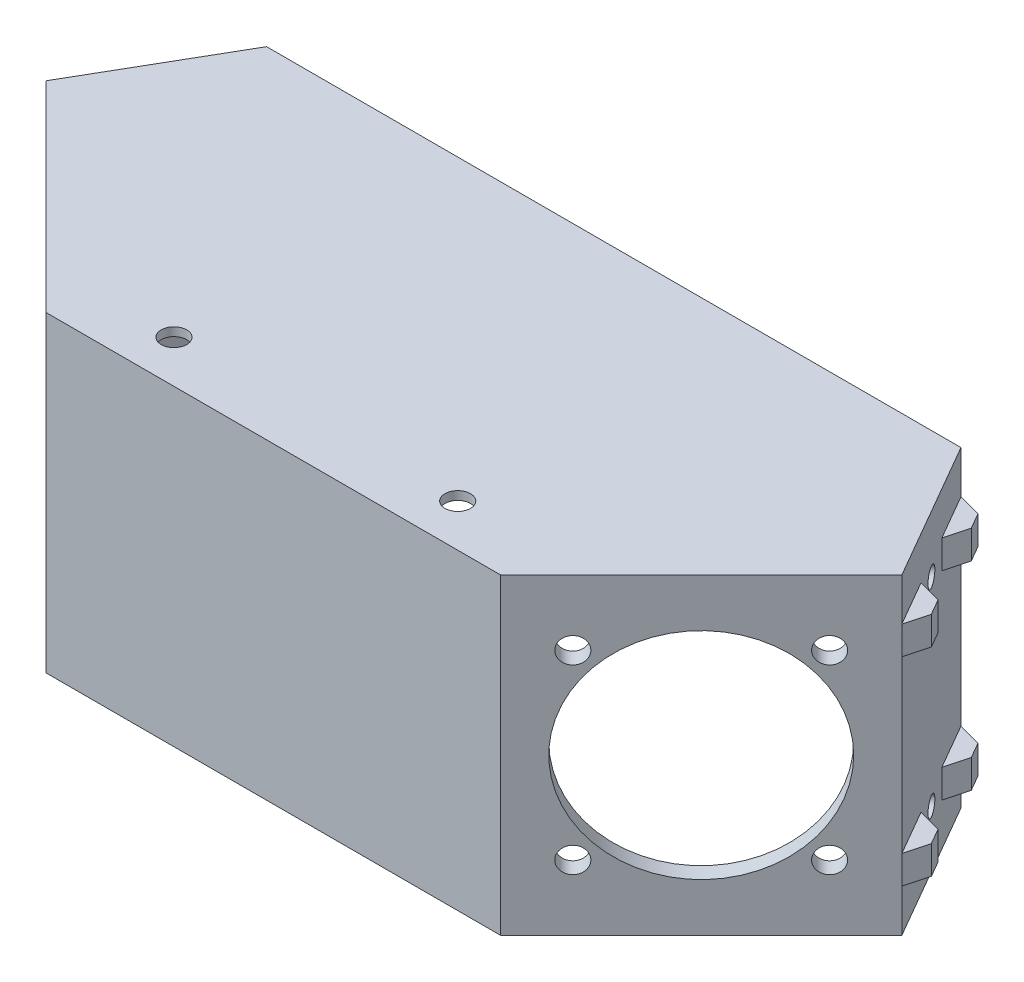
SolidWorks part; units mm, degrees
ref_plane "Front Plane" through (0, 0, 0) normal (0, 0, 1) x (1, 0, 0)
ref_plane "Top Plane" through (0, 0, 0) normal (0, 1, 0) x (1, 0, 0)
ref_plane "Right Plane" through (0, 0, 0) normal (1, 0, 0) x (0, 0, -1)
sketch "Sketch1" plane through (0, 0, 0) normal (0, 1, 0) x (1, 0, 0)
  line L0 (-30, -18) -> (30, -18) construction
  line L1 (-30, 10) -> (-22.5, 10) construction
  line L2 (-46.46, 5.4904) -> (-53.96, -7.5) construction
  line L3 (-30, -10) -> (-22.5, -10) construction
  line L4 (30, 10) -> (30, 2.5) construction
  line L5 (0, 0) -> (0, -75.5561) construction
  line L6 (38.6603, -23) -> (51.362, -45) construction
  line L7 (56.8838, -52) -> (58.3716, -51.141) construction
  line L8 (59.1036, -48.409) -> (41.8357, -18.5) construction
  line L9 (43.1036, -13.7679) -> (55.6921, -6.5) construction
  line L10 (56.4241, -3.7679) -> (51.362, 5) construction
  line L11 (25.3812, 20) -> (-25.3812, 20) construction
  line L12 (43.5677, -13.5) -> (36.0677, -0.5096) construction
  line L13 (36.0677, -0.5096) -> (46.46, 5.4904) construction
  line L14 (46.46, 5.4904) -> (53.96, -7.5) construction
  line L15 (-36.0677, -0.5096) -> (-46.46, 5.4904) construction
  line L16 (-43.5677, -13.5) -> (-36.0677, -0.5096) construction
  line L17 (-56.4241, -3.7679) -> (-51.362, 5) construction
  line L18 (-43.1036, -13.7679) -> (-55.6921, -6.5) construction
  line L19 (-59.1036, -48.409) -> (-41.8357, -18.5) construction
  line L20 (-56.8838, -52) -> (-58.3716, -51.141) construction
  line L21 (-38.6603, -23) -> (-51.362, -45) construction
  line L22 (-30, 10) -> (-30, 2.5) construction
  line L23 (30, 2.5) -> (25, 2.5) construction
  line L24 (25, 2.5) -> (25, -2.5) construction
  line L25 (25, -2.5) -> (30, -2.5) construction
  line L26 (30, -2.5) -> (30, -10) construction
  line L27 (22.5, -10) -> (22.5, -5) construction
  line L28 (22.5, -5) -> (17.5, -5) construction
  line L29 (17.5, -5) -> (17.5, -10) construction
  line L30 (22.5, -10) -> (30, -10) construction
  line L31 (17.5, 10) -> (17.5, 9) construction
  line L32 (17.5, 9) -> (22.5, 9) construction
  line L33 (22.5, 9) -> (22.5, 10) construction
  line L34 (22.5, 10) -> (30, 10) construction
  line L35 (2.5, -10) -> (2.5, -5) construction
  line L36 (2.5, -5) -> (-2.5, -5) construction
  line L37 (-2.5, -5) -> (-2.5, -10) construction
  line L38 (-2.5, 10) -> (-2.5, 9) construction
  line L39 (-2.5, 9) -> (2.5, 9) construction
  line L40 (2.5, 9) -> (2.5, 10) construction
  line L41 (-17.5, -10) -> (-17.5, -5) construction
  line L42 (-17.5, -5) -> (-22.5, -5) construction
  line L43 (-22.5, -5) -> (-22.5, -10) construction
  line L44 (-22.5, 10) -> (-22.5, 9) construction
  line L45 (-22.5, 9) -> (-17.5, 9) construction
  line L46 (-17.5, 9) -> (-17.5, 10) construction
  line L47 (-17.5, 10) -> (-2.5, 10) construction
  line L48 (-17.5, -10) -> (-2.5, -10) construction
  line L49 (2.5, -10) -> (17.5, -10) construction
  line L50 (2.5, 10) -> (17.5, 10) construction
  line L51 (-25, -2.5) -> (-30, -2.5) construction
  line L52 (-25, 2.5) -> (-25, -2.5) construction
  line L53 (-30, 2.5) -> (-25, 2.5) construction
  line L54 (-30, -2.5) -> (-30, -10) construction
  line L55 (-56.8838, -52) -> (56.8838, -52) construction
  line L56 (-49.6299, -48) -> (49.6299, -48) construction
  line L57 (40.0502, -112) -> (-40.0502, -112)
  line L58 (-75.4055, -76.6447) -> (-61.1769, -52)
  line L59 (-75.4055, -76.6447) -> (-40.0502, -112)
  line L60 (-61.1769, -52) -> (61.1769, -52)
  line L61 (61.1769, -52) -> (75.4055, -76.6447)
  line L62 (75.4055, -76.6447) -> (40.0502, -112)
  circle A0 centre (0, 0) radius 31.6228 construction
  arc A1 (30, -18) -> (38.6603, -23) centre (30, -28) cw construction
  arc A2 (51.362, 5) -> (25.3812, 20) centre (25.3812, -10) ccw construction
  arc A3 (41.1036, -13.7679) -> (40.1036, -17.5) centre (40.1036, -15.5) ccw construction
  arc A4 (58.3716, -51.141) -> (59.1036, -48.409) centre (57.3716, -49.409) ccw construction
  arc A5 (55.6921, -6.5) -> (56.4241, -3.7679) centre (54.6921, -4.7679) ccw construction
  arc A6 (40.1036, -17.5) -> (41.8357, -18.5) centre (40.1036, -19.5) cw construction
  arc A7 (41.1036, -13.7679) -> (43.1036, -13.7679) centre (42.1036, -12.0359) ccw construction
  arc A8 (-41.1036, -13.7679) -> (-43.1036, -13.7679) centre (-42.1036, -12.0359) cw construction
  arc A9 (-40.1036, -17.5) -> (-41.8357, -18.5) centre (-40.1036, -19.5) ccw construction
  arc A10 (-55.6921, -6.5) -> (-56.4241, -3.7679) centre (-54.6921, -4.7679) cw construction
  arc A11 (-58.3716, -51.141) -> (-59.1036, -48.409) centre (-57.3716, -49.409) cw construction
  arc A12 (-41.1036, -13.7679) -> (-40.1036, -17.5) centre (-40.1036, -15.5) cw construction
  arc A13 (-51.362, 5) -> (-25.3812, 20) centre (-25.3812, -10) cw construction
  arc A14 (-30, -18) -> (-38.6603, -23) centre (-30, -28) ccw construction
  arc A17 (49.6299, -48) -> (51.362, -45) centre (49.6299, -46) ccw construction
  arc A18 (-49.6299, -48) -> (-51.362, -45) centre (-49.6299, -46) cw construction
  point P7 (-57.4241, -5.5)
  point P9 (0, -18)
  point P22 (35.7735, -18)
  point P27 (0, 10)
  point P30 (60.1036, -50.141)
  point P33 (57.4241, -5.5)
  point P61 (0, 20)
  point P65 (-60.1036, -50.141)
  point P66 (-35.7735, -18)
  dimension "D12" = 10
  dimension "D14" = 30
  dimension "D16" = 2
  dimension "D17" = 2
  dimension "D28" = 60
  dimension "D29" = 2
  dimension "D32" = 45
  dimension "D2" = 30
  dimension "D3" = 5
  dimension "D4" = 8
  dimension "D5" = 40
  dimension "D6" = 20
  dimension "D7" = 30
  dimension "D8" = 10
  dimension "D9" = 4
  dimension "D10" = 12
  dimension "D11" = 15
  dimension "D13" = 20
  dimension "D15" = 34
  dimension "D18" = 5
  dimension "D19" = 2.5
  dimension "D20" = 5
  dimension "D21" = 5
  dimension "D22" = 5
  dimension "D23" = 7.5
  dimension "D24" = 1
  dimension "D26" = 20
  dimension "D27" = 4
  dimension "D30" = 50
  dimension "D31" = 45
  dimension "D33" = 50
  dimension "D25" = 3
extrude "Boss-Extrude1" add sketch "Sketch1" along normal blind 55
shell "Shell1" thickness 3 removed face at (0, 0, 80.2149) removed face at (0, 27.5, 52)
sketch "Sketch2" plane through (76.0251, 0, 76.0251) normal (0.7071, 0, 0.7071) x (0.7071, 0, -0.7071)
  line L0 (-0.8762, 27.5) -> (-25.8762, 27.5) construction
  line L1 (-0.8762, 55) -> (-0.8762, 0) construction
  line L2 (-25.8762, 27.5) -> (-25.8762, 0) construction
  line L3 (-50.8762, 0) -> (-0.8762, 0) construction
  circle A0 centre (-25.8762, 27.5) radius 19
  circle A1 centre (-41.8762, 11.5) radius 2.25
  circle A2 centre (-9.8762, 11.5) radius 2.25
  circle A3 centre (-9.8762, 43.5) radius 2.25
  circle A4 centre (-41.8762, 43.5) radius 2.25
  dimension "D1" = 38
  dimension "D2" = 4.5
  dimension "D4" = 16
  dimension "D7" = 32
  dimension "D8" = 32
  dimension "D3" = 16
  dimension "D6" = 2
  dimension "D5" = 2
extrude "Cut-Extrude1" cut sketch "Sketch2" against normal up to next
sketch "Sketch3" plane through (23.366, 0, -13.4904) normal (0.866, 0, -0.5) x (-0.5, 0, -0.866)
  line L0 (-89.8504, 55) -> (-89.8504, 0) construction
  line L1 (-104.079, 55) -> (-75.6218, 55) construction
  line L2 (-104.079, 0) -> (-75.6218, 0) construction
  circle A0 centre (-89.8504, 10) radius 1.65
  circle A1 centre (-89.8504, 45) radius 1.65
  dimension "D1" = 3.3
  dimension "D2" = 3.3
  dimension "D4" = 10
  dimension "D3" = 10
extrude "Cut-Extrude2" cut sketch "Sketch3" against normal up to next
sketch "Sketch4" plane through (23.366, 0, -13.4904) normal (0.866, 0, -0.5) x (-0.5, 0, -0.866)
  line L0 (-75.6218, 55) -> (-75.6218, 0) construction
  line L1 (-75.6218, 7.5) -> (-84.8504, 7.5)
  line L2 (-75.6218, 7.5) -> (-75.6218, 12.5)
  line L3 (-75.6218, 12.5) -> (-84.8504, 12.5)
  line L4 (-104.079, 7.5) -> (-104.079, 12.5)
  line L5 (-104.079, 55) -> (-104.079, 0) construction
  line L6 (-104.079, 0) -> (-75.6218, 0) construction
  line L7 (-75.6218, 42.5) -> (-84.8504, 42.5)
  line L8 (-75.6218, 42.5) -> (-75.6218, 47.5)
  line L9 (-75.6218, 47.5) -> (-84.8504, 47.5)
  line L10 (-104.079, 42.5) -> (-104.079, 47.5)
  line L11 (-104.079, 55) -> (-75.6218, 55) construction
  line L12 (-84.8504, 47.5) -> (-84.8504, 42.5)
  line L13 (-94.8504, 47.5) -> (-94.8504, 42.5)
  line L14 (-94.8504, 47.5) -> (-104.079, 47.5)
  line L15 (-94.8504, 42.5) -> (-104.079, 42.5)
  line L16 (-94.8504, 12.5) -> (-104.079, 12.5)
  line L17 (-94.8504, 7.5) -> (-104.079, 7.5)
  line L18 (-94.8504, 12.5) -> (-94.8504, 7.5)
  line L19 (-84.8504, 12.5) -> (-84.8504, 7.5)
  circle A0 centre (-89.8504, 45) radius 1.65 construction
  dimension "D1" = 5
  dimension "D2" = 5
  dimension "D3" = 7.5
  dimension "D4" = 7.5
  dimension "D5" = 10
  dimension "D6" = 5
extrude "Boss-Extrude2" add sketch "Sketch4" along normal blind 3
chamfer "Chamfer1" distance 3 angle 45 8 edges at (63.775, 10, 50.5) (63.775, 45, 50.5) (68.3893, 45, 58.4922) (68.3893, 10, 58.4922) (73.3893, 10, 67.1525) (73.3893, 45, 67.1525) (78.0036, 10, 75.1447) (78.0036, 45, 75.1447)
mirror "Mirror2" about plane through (0, 0, 0) normal (1, 0, 0) of "Chamfer1", "Boss-Extrude2", "Cut-Extrude2", "Cut-Extrude1"
sketch "Sketch5" plane through (0, 55, 0) normal (0, 1, 0) x (1, 0, 0)
  line L0 (-132.9425, -111.5) -> (118.6256, -111.5) construction
  line L1 (61.1769, -52) -> (-61.1769, -52) construction
  line L2 (0, -52) -> (0, -112) construction
  line L3 (-40.0502, -112) -> (40.0502, -112) construction
  circle A0 centre (0, -246.5) radius 135 construction
  circle A1 centre (-25, -104.5) radius 2.25
  circle A2 centre (25, -104.5) radius 2.25
  dimension "D1" = 270
  dimension "D3" = 4.5
  dimension "D4" = 25
  dimension "D2" = 59.5
  dimension "D5" = 7.5
extrude "Cut-Extrude3" cut sketch "Sketch5" against normal through all
sketch "Sketch6" plane through (0, 52, 0) normal (0, -1, 0) x (1, 0, 0)
  line L0 (-57.7128, 52) -> (57.7128, 52)
  line L1 (57.7128, 52) -> (71.6564, 76.1511)
  line L2 (71.6564, 76.1511) -> (38.8075, 109)
  line L3 (38.8075, 109) -> (-38.8075, 109)
  line L4 (-38.8075, 109) -> (-71.6564, 76.1511)
  line L5 (-71.6564, 76.1511) -> (-57.7128, 52)
extrude "Cut-Extrude4" cut sketch "Sketch6" against normal blind 1.5
